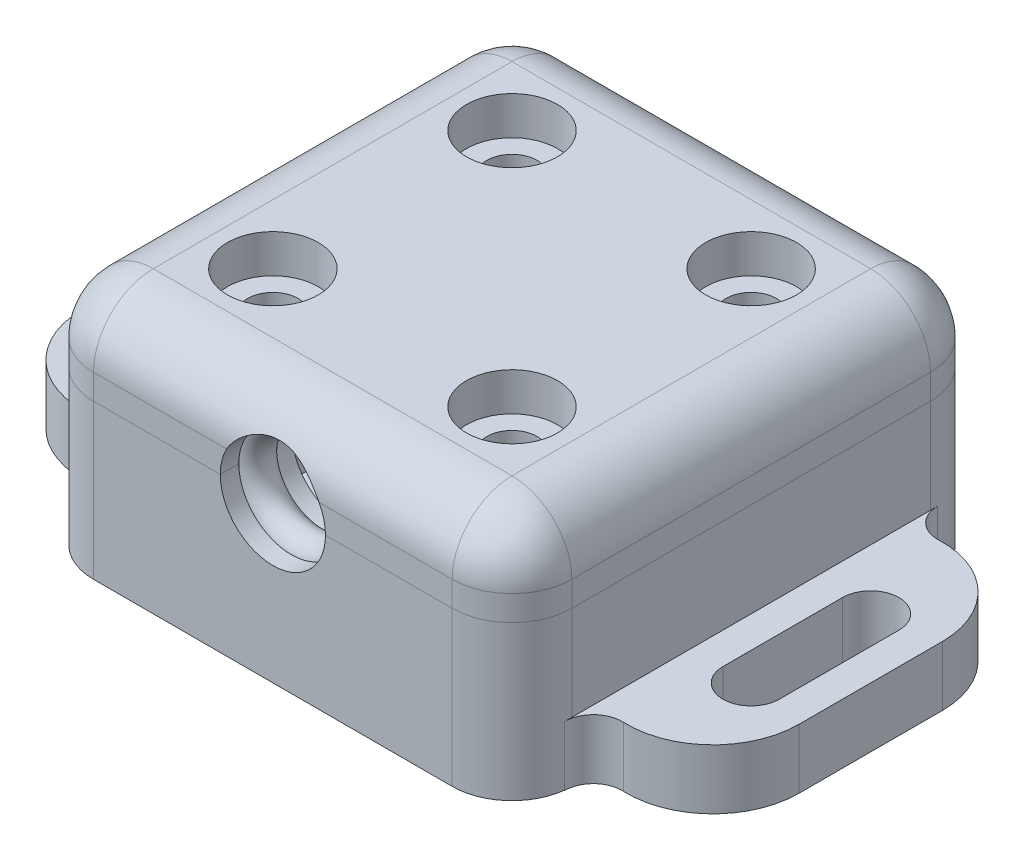
SolidWorks part; units mm, degrees
ref_plane "Front Plane" through (0, 0, 0) normal (0, 0, 1) x (1, 0, 0)
ref_plane "Top Plane" through (0, 0, 0) normal (0, 1, 0) x (1, 0, 0)
ref_plane "Right Plane" through (0, 0, 0) normal (1, 0, 0) x (0, 0, -1)
sketch "Sketch1" plane through (0, 0, 0) normal (0, 1, 0) x (1, 0, 0)
  line L5 (-8.89, -8.89) -> (8.89, -8.89)
  line L6 (-8.89, -8.89) -> (-8.89, 8.89)
  line L7 (-8.89, 8.89) -> (8.89, 8.89)
  line L8 (8.89, -8.89) -> (8.89, 8.89)
  line L9 (-8.89, -8.89) -> (8.89, 8.89) construction
  line L10 (-8.89, 8.89) -> (8.89, -8.89) construction
  line L11 (-12.7, -12.7) -> (12.7, -12.7)
  line L12 (-12.7, -12.7) -> (-12.7, 12.7)
  line L13 (-12.7, 12.7) -> (12.7, 12.7)
  line L14 (12.7, -12.7) -> (12.7, 12.7)
  line L15 (-12.7, -12.7) -> (12.7, 12.7) construction
  line L16 (-12.7, 12.7) -> (12.7, -12.7) construction
  point P0 (0, 0)
  point P6 (0, 0)
  dimension "D1" = 3.81
  dimension "D2" = 3.81
  dimension "D3" = 17.78
  dimension "D4" = 17.78
extrude "Boss-Extrude1" add sketch "Sketch1" along normal blind 4.2543
sketch "Sketch3" plane through (0, 0, 12.7) normal (0, 0, 1) x (1, 0, 0)
  line L0 (-12.7, 4.2543) -> (12.7, 4.2543) construction
  circle A0 centre (0, 4.2543) radius 2.794
  dimension "D1" = 5.588
extrude "Cut-Extrude1" cut sketch "Sketch3" against normal up to next
mirror "Mirror1" about plane through (0, 4.2543, 0) normal (0, -1, 0) of bodies 103
sketch "Sketch2" plane through (0, 0, 0) normal (0, -1, 0) x (1, 0, 0)
  line L0 (-12.7, 12.7) -> (12.7, 12.7) construction
  line L1 (12.7, -12.7) -> (-12.7, -12.7)
  line L2 (12.7, -12.7) -> (12.7, 12.7)
  line L3 (12.7, 12.7) -> (-12.7, 12.7)
  line L4 (-12.7, -12.7) -> (-12.7, 12.7)
  line L5 (12.7, -12.7) -> (-12.7, 12.7) construction
  line L6 (12.7, 12.7) -> (-12.7, -12.7) construction
  line L7 (-12.7, -12.7) -> (-12.7, 12.7) construction
  point P0 (0, 0)
extrude "Boss-Extrude2" add sketch "Sketch2" along normal blind 3.937
sketch "Sketch4" plane through (0, 4.2543, 0) normal (0, 1, 0) x (1, 0, 0)
  line L0 (2.794, -10.795) -> (9.525, -10.795)
  line L1 (2.794, -12.7) -> (2.794, -8.89) construction
  line L2 (10.795, -9.525) -> (10.795, 9.525)
  line L3 (9.525, 10.795) -> (-9.525, 10.795)
  line L4 (-10.795, 9.525) -> (-10.795, -9.525)
  line L5 (-9.525, -10.795) -> (-2.794, -10.795)
  line L6 (-2.794, -8.89) -> (-2.794, -12.7) construction
  line L7 (8.89, -8.89) -> (8.89, -10.795) construction
  line L8 (8.89, -10.795) -> (8.89, -8.89) construction
  line L9 (8.89, -8.89) -> (10.795, -8.89) construction
  line L10 (8.89, 8.89) -> (8.89, 10.795) construction
  line L11 (-8.89, 8.89) -> (-10.795, 8.89) construction
  arc A0 (9.525, -10.795) -> (10.795, -9.525) centre (9.525, -9.525) ccw
  arc A1 (-10.795, -9.525) -> (-9.525, -10.795) centre (-9.525, -9.525) ccw
  arc A2 (-9.525, 10.795) -> (-10.795, 9.525) centre (-9.525, 9.525) ccw
  arc A3 (10.795, 9.525) -> (9.525, 10.795) centre (9.525, 9.525) ccw
  dimension "D1" = 1.27
ref_plane "Plane1" through (2.794, 0, 0) normal (-1, 0, 0) x (0, 0, 1)
sketch "Sketch5" plane through (2.794, 0, 0) normal (-1, 0, 0) x (0, 0, 1)
  line L0 (12.7, 4.2543) -> (8.89, 4.2543) construction
  circle A0 centre (10.795, 4.2543) radius 0.9525
  dimension "D1" = 1.905
sketch "Sketch6" plane through (0, 4.2543, 0) normal (0, 1, 0) x (1, 0, 0)
  line L0 (-10.795, 9.525) -> (-10.795, -9.525) construction
  line L5 (9.525, 10.795) -> (-9.525, 10.795) construction
  line L6 (10.795, -9.525) -> (10.795, 9.525) construction
  line L7 (-10.795, 9.525) -> (-10.795, -9.525)
  line L8 (9.525, 10.795) -> (-9.525, 10.795)
  line L9 (10.795, -9.525) -> (10.795, 9.525)
  line L10 (-9.525, -10.795) -> (9.525, -10.795)
  arc A0 (-10.795, -9.525) -> (-9.525, -10.795) centre (-9.525, -9.525) ccw construction
  arc A1 (-9.525, 10.795) -> (-10.795, 9.525) centre (-9.525, 9.525) ccw construction
  arc A2 (10.795, 9.525) -> (9.525, 10.795) centre (9.525, 9.525) ccw construction
  arc A3 (9.525, -10.795) -> (10.795, -9.525) centre (9.525, -9.525) ccw construction
  arc A4 (-10.795, -9.525) -> (-9.525, -10.795) centre (-9.525, -9.525) ccw
  arc A5 (-9.525, 10.795) -> (-10.795, 9.525) centre (-9.525, 9.525) ccw
  arc A6 (10.795, 9.525) -> (9.525, 10.795) centre (9.525, 9.525) ccw
  arc A7 (9.525, -10.795) -> (10.795, -9.525) centre (9.525, -9.525) ccw
sweep "Cut-Sweep2" cut profiles "Sketch5" path "Sketch6"
sketch "Sketch7" plane through (0, 4.2543, 0) normal (0, 1, 0) x (1, 0, 0)
  line L0 (2.794, -9.8425) -> (9.525, -9.8425) construction
  line L1 (9.525, -11.7475) -> (2.794, -11.7475) construction
  line L2 (2.794, -9.8425) -> (2.794, -8.89) construction
  circle A0 centre (3.048, -10.795) radius 0.9525
  dimension "D1" = 0.254
ref_axis "Axis1" through (0, 4.2543, 8.89) along (0, 0, 1)
revolve "Cut-Revolve1" cut sketch "Sketch7" angle 360 about axis through (0, 4.2543, 8.89) along (0, 0, 1)
sweep "Sweep1" add profiles "Sketch5<2>" path "Sketch4"
sketch "Sketch5<2>" plane through (2.794, 0, 0) normal (-1, 0, 0) x (0, 0, 1) same geometry as "Sketch5"
revolve "Revolve1" add sketch "Sketch7<2>" angle 360 about axis through (0, 4.2543, 8.89) along (0, 0, 1)
sketch "Sketch7<2>" plane through (0, 4.2543, 0) normal (0, 1, 0) x (1, 0, 0) same geometry as "Sketch7"
ref_plane "Top of PCB" through (0, 1.6, 0) normal (0, 1, 0) x (1, 0, 0)
sketch "Sketch9" plane through (0, 8.5086, 0) normal (0, 1, 0) x (1, 0, 0)
  line L0 (-12.7, -12.7) -> (12.7, -12.7) construction
  line L1 (12.7, 12.7) -> (-12.7, 12.7)
  line L2 (12.7, 12.7) -> (12.7, -12.7)
  line L3 (12.7, -12.7) -> (-12.7, -12.7)
  line L4 (-12.7, 12.7) -> (-12.7, -12.7)
  line L5 (12.7, 12.7) -> (-12.7, -12.7) construction
  line L6 (12.7, -12.7) -> (-12.7, 12.7) construction
  line L7 (-12.7, 12.7) -> (-12.7, -12.7) construction
  point P0 (0, 0)
extrude "Boss-Extrude3" add sketch "Sketch9" along normal blind 0.254
sketch "Sketch13" plane through (0, 8.5086, 0) normal (0, -1, 0) x (1, 0, 0)
  line L1 (8.89, -8.89) -> (-8.89, -8.89)
  line L2 (8.89, -8.89) -> (8.89, 8.89)
  line L3 (8.89, 8.89) -> (-8.89, 8.89)
  line L4 (-8.89, -8.89) -> (-8.89, 8.89)
  line L5 (8.89, -8.89) -> (-8.89, 8.89) construction
  line L6 (8.89, 8.89) -> (-8.89, -8.89) construction
  point P0 (0, 0)
extrude "Boss-Extrude5" add sketch "Sketch13" along normal blind 1.6
sketch "Sketch10" plane through (0, 6.9086, 0) normal (0, -1, 0) x (1, 0, 0)
  line L1 (8.89, -8.89) -> (-8.89, -8.89) construction
  line L2 (0, 0) -> (0, -50000) construction
  line L3 (0, 0) -> (-50000, 0) construction
  line L8 (6.35, -3.302) -> (8.89, -3.302)
  line L9 (3.302, -6.35) -> (3.302, -8.89)
  line L10 (3.302, -8.89) -> (8.89, -8.89)
  line L11 (8.89, -8.89) -> (8.89, -3.302)
  line L12 (-8.89, -8.89) -> (-8.89, -3.302)
  line L13 (-3.302, -8.89) -> (-8.89, -8.89)
  line L14 (-3.302, -6.35) -> (-3.302, -8.89)
  line L15 (-6.35, -3.302) -> (-8.89, -3.302)
  line L16 (-6.35, 3.302) -> (-8.89, 3.302)
  line L17 (-3.302, 6.35) -> (-3.302, 8.89)
  line L18 (-3.302, 8.89) -> (-8.89, 8.89)
  line L19 (-8.89, 8.89) -> (-8.89, 3.302)
  line L20 (8.89, 8.89) -> (8.89, 3.302)
  line L21 (3.302, 8.89) -> (8.89, 8.89)
  line L22 (3.302, 6.35) -> (3.302, 8.89)
  line L23 (6.35, 3.302) -> (8.89, 3.302)
  line L24 (8.89, 8.89) -> (8.89, -8.89) construction
  arc A0 (6.35, -3.302) -> (3.302, -6.35) centre (6.35, -6.35) ccw
  arc A1 (-6.35, -3.302) -> (-3.302, -6.35) centre (-6.35, -6.35) cw
  arc A2 (-6.35, 3.302) -> (-3.302, 6.35) centre (-6.35, 6.35) ccw
  arc A3 (6.35, 3.302) -> (3.302, 6.35) centre (6.35, 6.35) cw
  dimension "D3" = 3.048
  dimension "D1" = 2.54
  dimension "D2" = 2.54
extrude "Boss-Extrude4" add sketch "Sketch10" along normal up to surface (5.3086 mm away) up to plane "Top of PCB"
sketch "Sketch11" plane through (0, 1.6, 0) normal (0, -1, 0) x (1, 0, 0)
  line L0 (0, 0) -> (0, 50000) construction
  line L1 (0, 0) -> (50000, 0) construction
  circle A0 centre (6.35, 6.35) radius 1.3335
  circle A2 centre (6.35, -6.35) radius 1.3335
  circle A3 centre (-6.35, 6.35) radius 1.3335
  circle A4 centre (-6.35, -6.35) radius 1.3335
  arc A5 (3.302, 6.35) -> (6.35, 3.302) centre (6.35, 6.35) ccw construction
  dimension "D1" = 2.667
extrude "Cut-Extrude2" cut sketch "Sketch11" against normal through all
sketch "Sketch12" plane through (0, 8.7626, 0) normal (0, 1, 0) x (1, 0, 0)
  line L0 (0, 0) -> (0, -50000) construction
  line L1 (0, 0) -> (-50000, 0) construction
  circle A0 centre (-6.35, -6.35) radius 2.413
  circle A1 centre (-6.35, -6.35) radius 1.3335 construction
  circle A2 centre (-6.35, 6.35) radius 2.413
  circle A3 centre (6.35, -6.35) radius 2.413
  circle A4 centre (6.35, 6.35) radius 2.413
  dimension "D1" = 4.826
extrude "Cut-Extrude3" cut sketch "Sketch12" against normal blind 2.032
fillet "Fillet2" radius 3.175 8 edges at (12.7, 6.5085, -12.7) (-12.7, 6.5085, -12.7) (-12.7, 6.5085, 12.7) (12.7, 6.5085, 12.7) (12.7, 8.7626, 0) (0, 8.7626, -12.7) (-12.7, 8.7626, 0) (0, 8.7626, 12.7)
fillet "Fillet3" radius 3.175 12 edges at (3.302, 6.9086, 7.62) (7.62, 6.9086, 3.302) (7.62, 6.9086, -3.302) (3.302, 6.9086, -7.62) (-7.62, 6.9086, 3.302) (-3.302, 6.9086, 7.62) (-7.62, 6.9086, -3.302) (-4.1947, 6.9086, -4.1947) (4.1947, 6.9086, 4.1947) (4.1947, 6.9086, -4.1947) (-4.1947, 6.9086, 4.1947) (-3.302, 6.9086, -7.62)
fillet "Fillet4" radius 0.508 8 edges at (-6.096, 1.6, -8.89) (-8.89, 1.6, -6.096) (-8.89, 1.6, 6.096) (-6.096, 1.6, 8.89) (8.89, 1.6, 6.096) (6.096, 1.6, 8.89) (8.89, 1.6, -6.096) (6.096, 1.6, -8.89)
extrude "Cut-Extrude5" cut sketch "Sketch11<2>" along normal blind 4.572 draft 4
sketch "Sketch11<2>" plane through (0, 1.6, 0) normal (0, -1, 0) x (1, 0, 0) same geometry as "Sketch11"
fillet "Fillet5" radius 3.175 4 edges at (-12.7, 0.1586, -12.7) (-12.7, 0.1586, 12.7) (12.7, 0.1586, -12.7) (12.7, 0.1586, 12.7)
sketch "Sketch14" plane through (0, -3.937, 0) normal (0, -1, 0) x (1, 0, 0)
  line L0 (12.7, 9.9007) -> (12.7, -9.9007)
  line L1 (12.7, -9.525) -> (12.7, 9.525) construction
  line L3 (0, 0) -> (50000, 0) construction
  line L4 (19.05, -3.81) -> (19.05, 3.81)
  line L5 (15.875, 3.175) -> (15.875, -3.175) construction
  line L6 (17.375, 3.175) -> (17.375, -3.175)
  line L7 (14.375, 3.175) -> (14.375, -3.175)
  line L8 (15.875, -1.0957) -> (12.7, -1.0957) construction
  line L9 (12.7, -1.0957) -> (15.875, -1.0957) construction
  line L10 (15.875, -1.0957) -> (19.05, -1.0957) construction
  line L11 (0, 0) -> (0, 50000) construction
  line L12 (-15.875, 3.175) -> (-15.875, -3.175) construction
  line L13 (-17.375, 3.175) -> (-17.375, -3.175)
  line L14 (-14.375, 3.175) -> (-14.375, -3.175)
  line L15 (-15.875, -1.0957) -> (-19.05, -1.0957) construction
  line L16 (-12.7, -1.0957) -> (-15.875, -1.0957) construction
  line L17 (-15.875, -1.0957) -> (-12.7, -1.0957) construction
  line L18 (-19.05, -3.81) -> (-19.05, 3.81)
  line L19 (-12.7, 9.9007) -> (-12.7, -9.9007)
  arc A0 (12.7, -9.9007) -> (14.2875, -8.378) centre (14.224, -9.9007) cw
  arc A3 (14.2875, -8.378) -> (19.05, -3.81) centre (14.478, -3.81) ccw
  arc A4 (14.2875, 8.378) -> (19.05, 3.81) centre (14.478, 3.81) cw
  arc A5 (12.7, 9.9007) -> (14.2875, 8.378) centre (14.224, 9.9007) ccw
  arc A6 (17.375, 3.175) -> (14.375, 3.175) centre (15.875, 3.175) ccw
  arc A7 (14.375, -3.175) -> (17.375, -3.175) centre (15.875, -3.175) ccw
  arc A8 (-17.375, 3.175) -> (-14.375, 3.175) centre (-15.875, 3.175) cw
  arc A9 (-14.375, -3.175) -> (-17.375, -3.175) centre (-15.875, -3.175) cw
  arc A10 (-12.7, 9.9007) -> (-14.2875, 8.378) centre (-14.224, 9.9007) cw
  arc A11 (-14.2875, 8.378) -> (-19.05, 3.81) centre (-14.478, 3.81) ccw
  arc A12 (-14.2875, -8.378) -> (-19.05, -3.81) centre (-14.478, -3.81) cw
  arc A13 (-12.7, -9.9007) -> (-14.2875, -8.378) centre (-14.224, -9.9007) ccw
  point P7 (12.7, 0)
  point P17 (19.05, 0)
  point P19 (15.875, 0)
  point P31 (-15.875, 0)
  point P49 (-19.05, 0)
  point P50 (-12.7, 0)
  dimension "D1" = 1.524
  dimension "D2" = 4.572
  dimension "D6" = 1.5
  dimension "D3" = 6.35
  dimension "D4" = 7.62
  dimension "D5" = 6.35
extrude "Boss-Extrude6" add sketch "Sketch14" against normal blind 3.175
